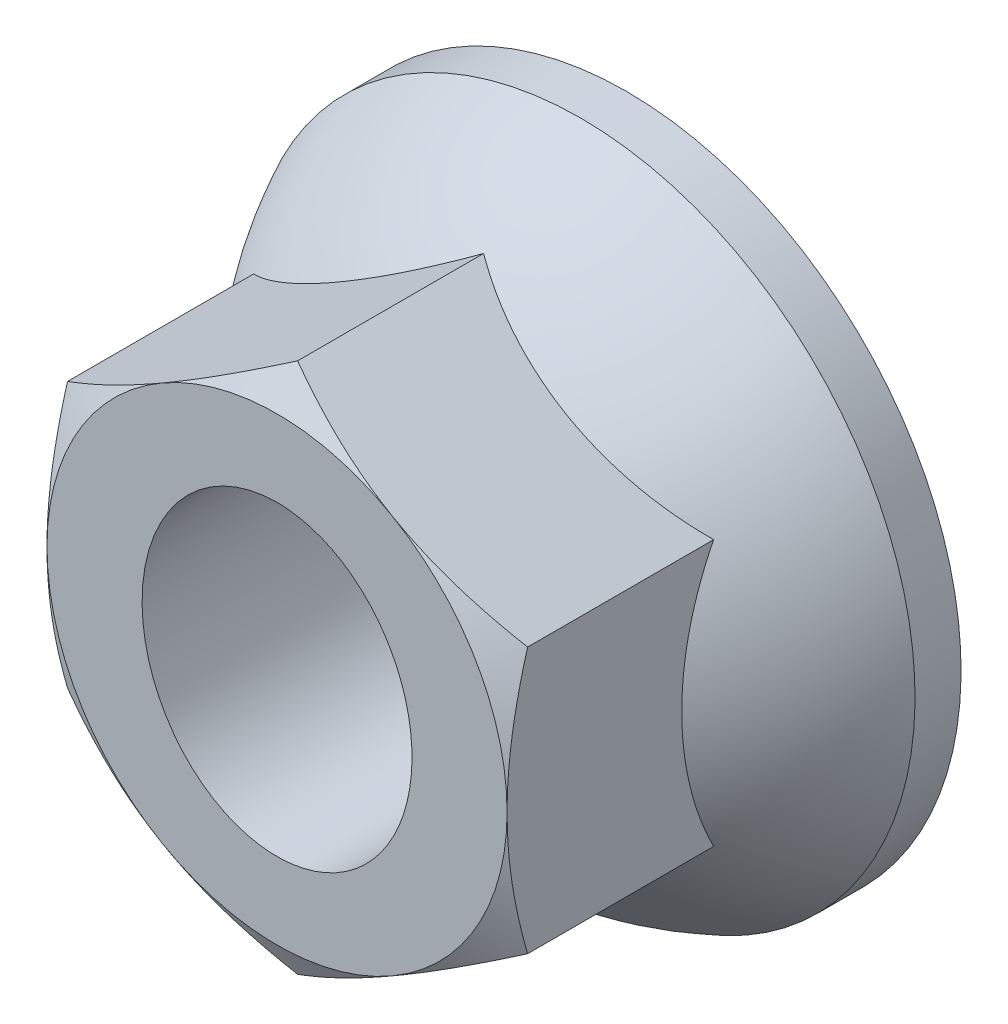
SolidWorks part; units mm, degrees
ref_plane "Front" through (0, 0, 0) normal (0, 0, 1) x (1, 0, 0)
ref_plane "Top" through (0, 0, 0) normal (0, 1, 0) x (1, 0, 0)
ref_plane "Right" through (0, 0, 0) normal (1, 0, 0) x (0, 0, -1)
sketch "Sketch1" plane through (0, 0, 0) normal (1, 0, 0) x (0, 0, -1)
  line L0 (0, 0) -> (5.7, 0) construction
  line L1 (0, 0) -> (-5.7, 0) construction
  line L2 (-5.7, 0) -> (-5.7, 7.5) construction
  line L3 (-5.7, 0) -> (-5.7, -7.5) construction
  line L4 (5.7, 0) -> (5.7, 5) construction
  line L5 (5.7, 0) -> (5.7, -5) construction
  line L6 (5.6062, 5.1624) -> (6.3562, 3.8633) construction
  line L7 (6.3562, 3.8633) -> (7.1062, 5.1624) construction
  line L8 (7.1062, 5.1624) -> (5.6062, 5.1624) construction
  line L9 (6.3562, 5.1624) -> (6.3562, 5) construction
  line L10 (6.3562, 5) -> (6.3562, 4.0257) construction
  line L11 (6.3562, 4.0257) -> (6.3562, 3.8633) construction
  line L12 (6.3562, 5.0812) -> (7.0594, 5.0812) construction
  line L13 (6.3562, 5.0812) -> (5.6531, 5.0812) construction
  line L14 (5.7, 5) -> (7.0125, 5) construction
  line L15 (6.2625, 4.0257) -> (6.45, 4.0257) construction
  line L20 (5.7, -5) -> (5.7, -10.9) construction
  line L21 (5.7, 5) -> (5.7, 10.9) construction
  line L22 (5.7, 10.9) -> (4.2, 10.9) construction
  line L23 (4.2, 10.9) -> (4.2, 0) construction
  line L24 (4.2, 10.9) -> (-2.6, 10.9) construction
  line L25 (-2.6, 10.9) -> (-2.6, 0) construction
  dimension "Height" = 11.4
  dimension "Width" = 15
  dimension "Thread Size" = 10
  dimension "Thread Pitch" = 1.5
  dimension "D2" = 0.1875
  dimension "Flange Diameter" = 21.8
  dimension "Flange Thickness" = 1.5
  dimension "Hex Height" = 3.1
sketch "Sketch20" plane through (0, 0, 0) normal (0, 0, 1) x (1, 0, 0)
  line L1 (7.5, -4.3301) -> (7.5, 4.3301)
  line L2 (7.5, 4.3301) -> (0, 8.6603)
  line L3 (0, 8.6603) -> (-7.5, 4.3301)
  line L4 (-7.5, 4.3301) -> (-7.5, -4.3301)
  line L5 (-7.5, -4.3301) -> (0, -8.6603)
  line L6 (0, -8.6603) -> (7.5, -4.3301)
  circle A0 centre (0, 0) radius 7.5 construction
  circle A1 centre (0, 0) radius 10.9 construction
  point P10 (0, 10.9)
  dimension "Flange OD" = 21.8
  dimension "Hex" = 15
extrude "Extrude1" add sketch "Sketch20" along normal mid plane 11.4
sketch "Sketch18" plane through (0, 0, 0) normal (1, 0, 0) x (0, 0, -1)
  line L0 (5.7, 0) -> (5.7, 10.9)
  line L1 (5.7, 10.9) -> (4.2, 10.9)
  line L2 (-2.6, 0) -> (5.7, 0) construction
  line L3 (-2.6, 0) -> (-2.6, -0.745) construction
  line L4 (5.7, -4.3301) -> (5.7, 4.3301) construction
  line L6 (5.7, 0) -> (-2.6, 0)
  arc A0 (4.2, 10.9) -> (-2.6, 0) centre (9.536, 0) ccw
  dimension "Flange Thickness" = 1.5
revolve "Revolve1" add sketch "Sketch18" angle 360 about L6
sketch "Sketch2" plane through (0, 0, 5.7) normal (0, 0, 1) x (1, 0, 0)
  circle A0 centre (0, 0) radius 7.5 construction
  circle A5 centre (0, 0) radius 7.5
extrude "Cut-Extrude1" cut sketch "Sketch2" against normal through all draft 60 flip side to cut
sketch "Sketch4" plane through (0, 0, -5.7) normal (0, 0, -1) x (-1, 0, 0)
  line L0 (5, 0) -> (4.4, 0) construction
  circle A0 centre (0, 0) radius 5
  circle A1 centre (0, 0) radius 4.4 construction
  dimension "Thread OD" = 10
  dimension "D1" = 0.6
sketch "Sketch5" plane through (0, 0, 5.7) normal (0, 0, -1) x (-1, 0, 0)
  circle A2 centre (0, 0) radius 5 construction
  circle A3 centre (0, 0) radius 5
sketch "Sketch7" [suppressed] plane through (0, 0, -5.7) normal (0, 0, -1) x (-1, 0, 0)
  circle A0 centre (0, 0) radius 5 construction
  circle A1 centre (0, 0) radius 5
extrude "Cut-Extrude10" cut sketch "Sketch5" along normal through all
sketch "Sketch16" plane through (0, 0, 5.7) normal (0, 0, 1) x (1, 0, 0)
  circle A0 centre (0, 0) radius 7.5
  circle A1 centre (0, 0) radius 7.5 construction
  circle A2 centre (0, 0) radius 5 construction
  circle A3 centre (0, 0) radius 4.4 construction
  ellipse E0 centre (0, 0) end of major axis (0, 5) minor radius 4.4
  point P14 (0, -5)
extrude "Extrude2" add sketch "Sketch16" against normal up to surface (11.4 mm away) up to face at (0, 10.9, -5.7)
curve "Helix/Spiral1" [suppressed] pitch 1.5 height 12.9 turns 8.6 parameters "pitch"=1.5
sketch "Sketch9" [suppressed] plane through (0, 0, -7.9375) normal (1, 0, 0) x (0, 0, -1)
  line L0 (-2.2844, 5.0812) -> (-1.675, 4.0257)
  line L1 (-1.675, 4.0257) -> (-1.4875, 4.0257)
  line L2 (-1.4875, 4.0257) -> (-0.8781, 5.0812)
  line L3 (-0.8781, 5.0812) -> (-2.2844, 5.0812)
sweep "Sweep1" [suppressed] add profiles "Sketch9" path "Helix/Spiral1"
sketch "Sketch10" [suppressed] plane through (0, 0, -5.7) normal (0, 0, -1) x (-1, 0, 0)
  line L6 (-7.5, 4.3301) -> (-7.5, -4.3301)
  line L7 (0, 8.6603) -> (-7.5, 4.3301)
  line L8 (7.5, 4.3301) -> (0, 8.6603)
  line L9 (7.5, -4.3301) -> (7.5, 4.3301)
  line L10 (0, -8.6603) -> (7.5, -4.3301)
  line L11 (-7.5, -4.3301) -> (0, -8.6603)
  line L12 (-7.5, 4.3301) -> (-7.5, -4.3301)
  line L13 (0, 8.6603) -> (-7.5, 4.3301)
  line L14 (7.5, 4.3301) -> (0, 8.6603)
  line L15 (7.5, -4.3301) -> (7.5, 4.3301)
  line L16 (0, -8.6603) -> (7.5, -4.3301)
  line L17 (-7.5, -4.3301) -> (0, -8.6603)
  dimension "D1" = 0
extrude "Cut-Extrude4" [suppressed] cut sketch "Sketch10" along normal through all
sketch "Sketch11" [suppressed] plane through (0, 0, 5.7) normal (0, 0, 1) x (1, 0, 0)
  line L6 (7.5, -4.3301) -> (7.5, 4.3301)
  line L7 (7.5, 4.3301) -> (0, 8.6603)
  line L8 (0, 8.6603) -> (-7.5, 4.3301)
  line L9 (-7.5, 4.3301) -> (-7.5, -4.3301)
  line L10 (-7.5, -4.3301) -> (0, -8.6603)
  line L11 (0, -8.6603) -> (7.5, -4.3301)
  line L12 (7.5, -4.3301) -> (7.5, 4.3301)
  line L13 (7.5, 4.3301) -> (0, 8.6603)
  line L14 (0, 8.6603) -> (-7.5, 4.3301)
  line L15 (-7.5, 4.3301) -> (-7.5, -4.3301)
  line L16 (-7.5, -4.3301) -> (0, -8.6603)
  line L17 (0, -8.6603) -> (7.5, -4.3301)
  dimension "D1" = 0
extrude "Cut-Extrude5" [suppressed] cut sketch "Sketch11" along normal through all
sketch "Sketch13" [suppressed] plane through (0, 0, 5.7) normal (0, 0, 1) x (1, 0, 0)
  spline S0 degree 3 poles (-0.3161, -5.0762) (0.3161, -5.0762) (0.6258, -5.0387) (1.2327, -4.8926) (1.5319, -4.7823) (2.0899, -4.5024) (2.3537, -4.3314) (2.8434, -3.9355) (3.0645, -3.715) (3.4632, -3.2332) (3.6412, -2.9702) (3.9434, -2.4238) (4.0695, -2.1384) (4.2734, -1.5439) (4.3497, -1.2387) (4.4508, -0.6242) (4.4763, -0.3132) (4.476, 0.6313) (4.3757, 1.246) (4.0694, 2.1385) (3.9425, 2.4252) (3.6424, 2.9682) (3.4686, 3.2259) (3.0686, 3.7108) (2.8456, 3.933) (2.3639, 4.3238) (2.1037, 4.4945) (1.5393, 4.7795) (1.2466, 4.888) (0.7934, 4.9989) (0.6398, 5.0273) (0.3275, 5.0657) (0.169, 5.0757) (-0.3005, 5.0772) (-0.6105, 5.0413) (-1.224, 4.8957) (-1.52, 4.7872) (-2.0798, 4.5085) (-2.3476, 4.3355) (-2.8352, 3.9429) (-3.0575, 3.7227) (-3.461, 3.2367) (-3.6367, 2.9774) (-3.9399, 2.431) (-4.0684, 2.1408) (-4.2723, 1.548) (-4.3482, 1.2454) (-4.4504, 0.6285) (-4.4762, 0.3119) (-4.4762, -0.3131) (-4.4509, -0.6234) (-4.3495, -1.2397) (-4.2722, -1.5481) (-4.0692, -2.1387) (-3.9437, -2.4229) (-3.6423, -2.9684) (-3.4639, -3.2323) (-3.0656, -3.7138) (-2.8458, -3.933) (-2.3616, -4.3255) (-2.0937, -4.5002) (-1.5359, -4.7806) (-1.2443, -4.889) (-0.6335, -5.0376) (-0.3161, -5.0762) (0.3161, -5.0762) (0.6258, -5.0387) knots -0.03125 -0.03125 0 0 0.03125 0.03125 0.0625 0.0625 0.09375 0.09375 0.125 0.125 0.15625 0.15625 0.1875 0.1875 0.21875 0.21875 0.25 0.25 0.3125 0.3125 0.34375 0.34375 0.375 0.375 0.40625 0.40625 0.4375 0.4375 0.46875 0.46875 0.484375 0.484375 0.5 0.5 0.53125 0.53125 0.5625 0.5625 0.59375 0.59375 0.625 0.625 0.65625 0.65625 0.6875 0.6875 0.71875 0.71875 0.75 0.75 0.78125 0.78125 0.8125 0.8125 0.84375 0.84375 0.875 0.875 0.90625 0.90625 0.9375 0.9375 0.96875 0.96875 1 1 1.03125 1.03125 1.0625 only from (0, -5.0762) to (0, -5.0762)
  spline S1 degree 3 poles (-0.3161, -5.0762) (0.3161, -5.0762) (0.6258, -5.0387) (1.2327, -4.8926) (1.5319, -4.7823) (2.0899, -4.5024) (2.3537, -4.3314) (2.8434, -3.9355) (3.0645, -3.715) (3.4632, -3.2332) (3.6412, -2.9702) (3.9434, -2.4238) (4.0695, -2.1384) (4.2734, -1.5439) (4.3497, -1.2387) (4.4508, -0.6242) (4.4763, -0.3132) (4.476, 0.6313) (4.3757, 1.246) (4.0694, 2.1385) (3.9425, 2.4252) (3.6424, 2.9682) (3.4686, 3.2259) (3.0686, 3.7108) (2.8456, 3.933) (2.3639, 4.3238) (2.1037, 4.4945) (1.5393, 4.7795) (1.2466, 4.888) (0.7934, 4.9989) (0.6398, 5.0273) (0.3275, 5.0657) (0.169, 5.0757) (-0.3005, 5.0772) (-0.6105, 5.0413) (-1.224, 4.8957) (-1.52, 4.7872) (-2.0798, 4.5085) (-2.3476, 4.3355) (-2.8352, 3.9429) (-3.0575, 3.7227) (-3.461, 3.2367) (-3.6367, 2.9774) (-3.9399, 2.431) (-4.0684, 2.1408) (-4.2723, 1.548) (-4.3482, 1.2454) (-4.4504, 0.6285) (-4.4762, 0.3119) (-4.4762, -0.3131) (-4.4509, -0.6234) (-4.3495, -1.2397) (-4.2722, -1.5481) (-4.0692, -2.1387) (-3.9437, -2.4229) (-3.6423, -2.9684) (-3.4639, -3.2323) (-3.0656, -3.7138) (-2.8458, -3.933) (-2.3616, -4.3255) (-2.0937, -4.5002) (-1.5359, -4.7806) (-1.2443, -4.889) (-0.6335, -5.0376) (-0.3161, -5.0762) (0.3161, -5.0762) (0.6258, -5.0387) knots -0.03125 -0.03125 0 0 0.03125 0.03125 0.0625 0.0625 0.09375 0.09375 0.125 0.125 0.15625 0.15625 0.1875 0.1875 0.21875 0.21875 0.25 0.25 0.3125 0.3125 0.34375 0.34375 0.375 0.375 0.40625 0.40625 0.4375 0.4375 0.46875 0.46875 0.484375 0.484375 0.5 0.5 0.53125 0.53125 0.5625 0.5625 0.59375 0.59375 0.625 0.625 0.65625 0.65625 0.6875 0.6875 0.71875 0.71875 0.75 0.75 0.78125 0.78125 0.8125 0.8125 0.84375 0.84375 0.875 0.875 0.90625 0.90625 0.9375 0.9375 0.96875 0.96875 1 1 1.03125 1.03125 1.0625 only from (0, -5.0762) to (0, -5.0762)
  dimension "D1" = 0.0762
extrude "Cut-Extrude8" [suppressed] cut sketch "Sketch13" against normal blind 2.625 draft 45
sketch "Sketch14" [suppressed] plane through (0, 0, -5.7) normal (0, 0, -1) x (-1, 0, 0)
  spline S1 degree 3 poles (-0.3161, -5.0762) (0.3161, -5.0762) (0.6335, -5.0376) (1.2443, -4.889) (1.5359, -4.7806) (2.0937, -4.5002) (2.3616, -4.3255) (2.8458, -3.933) (3.0656, -3.7138) (3.4639, -3.2323) (3.6423, -2.9684) (3.9437, -2.4229) (4.0692, -2.1387) (4.2722, -1.5481) (4.3495, -1.2397) (4.4509, -0.6234) (4.4762, -0.3131) (4.4762, 0.3119) (4.4504, 0.6285) (4.3482, 1.2454) (4.2723, 1.548) (4.0684, 2.1408) (3.9399, 2.431) (3.6367, 2.9774) (3.461, 3.2367) (3.0575, 3.7227) (2.8352, 3.9429) (2.3476, 4.3355) (2.0798, 4.5085) (1.52, 4.7872) (1.224, 4.8957) (0.6105, 5.0413) (0.3005, 5.0772) (-0.169, 5.0757) (-0.3275, 5.0657) (-0.6398, 5.0273) (-0.7934, 4.9989) (-1.2466, 4.888) (-1.5393, 4.7795) (-2.1037, 4.4945) (-2.3639, 4.3238) (-2.8456, 3.933) (-3.0686, 3.7108) (-3.4686, 3.2259) (-3.6424, 2.9682) (-3.9425, 2.4252) (-4.0694, 2.1385) (-4.3757, 1.246) (-4.476, 0.6313) (-4.4763, -0.3132) (-4.4508, -0.6242) (-4.3497, -1.2387) (-4.2734, -1.5439) (-4.0695, -2.1384) (-3.9434, -2.4238) (-3.6412, -2.9702) (-3.4632, -3.2332) (-3.0645, -3.715) (-2.8434, -3.9355) (-2.3537, -4.3314) (-2.0899, -4.5024) (-1.5319, -4.7823) (-1.2327, -4.8926) (-0.6258, -5.0387) (-0.3161, -5.0762) (0.3161, -5.0762) (0.6335, -5.0376) knots -0.03125 -0.03125 0 0 0.03125 0.03125 0.0625 0.0625 0.09375 0.09375 0.125 0.125 0.15625 0.15625 0.1875 0.1875 0.21875 0.21875 0.25 0.25 0.28125 0.28125 0.3125 0.3125 0.34375 0.34375 0.375 0.375 0.40625 0.40625 0.4375 0.4375 0.46875 0.46875 0.5 0.5 0.515625 0.515625 0.53125 0.53125 0.5625 0.5625 0.59375 0.59375 0.625 0.625 0.65625 0.65625 0.6875 0.6875 0.75 0.75 0.78125 0.78125 0.8125 0.8125 0.84375 0.84375 0.875 0.875 0.90625 0.90625 0.9375 0.9375 0.96875 0.96875 1 1 1.03125 1.03125 1.0625 only from (0, -5.0762) to (0, -5.0762)
  spline S2 degree 3 poles (-0.3161, -5.0762) (0.3161, -5.0762) (0.6335, -5.0376) (1.2443, -4.889) (1.5359, -4.7806) (2.0937, -4.5002) (2.3616, -4.3255) (2.8458, -3.933) (3.0656, -3.7138) (3.4639, -3.2323) (3.6423, -2.9684) (3.9437, -2.4229) (4.0692, -2.1387) (4.2722, -1.5481) (4.3495, -1.2397) (4.4509, -0.6234) (4.4762, -0.3131) (4.4762, 0.3119) (4.4504, 0.6285) (4.3482, 1.2454) (4.2723, 1.548) (4.0684, 2.1408) (3.9399, 2.431) (3.6367, 2.9774) (3.461, 3.2367) (3.0575, 3.7227) (2.8352, 3.9429) (2.3476, 4.3355) (2.0798, 4.5085) (1.52, 4.7872) (1.224, 4.8957) (0.6105, 5.0413) (0.3005, 5.0772) (-0.169, 5.0757) (-0.3275, 5.0657) (-0.6398, 5.0273) (-0.7934, 4.9989) (-1.2466, 4.888) (-1.5393, 4.7795) (-2.1037, 4.4945) (-2.3639, 4.3238) (-2.8456, 3.933) (-3.0686, 3.7108) (-3.4686, 3.2259) (-3.6424, 2.9682) (-3.9425, 2.4252) (-4.0694, 2.1385) (-4.3757, 1.246) (-4.476, 0.6313) (-4.4763, -0.3132) (-4.4508, -0.6242) (-4.3497, -1.2387) (-4.2734, -1.5439) (-4.0695, -2.1384) (-3.9434, -2.4238) (-3.6412, -2.9702) (-3.4632, -3.2332) (-3.0645, -3.715) (-2.8434, -3.9355) (-2.3537, -4.3314) (-2.0899, -4.5024) (-1.5319, -4.7823) (-1.2327, -4.8926) (-0.6258, -5.0387) (-0.3161, -5.0762) (0.3161, -5.0762) (0.6335, -5.0376) knots -0.03125 -0.03125 0 0 0.03125 0.03125 0.0625 0.0625 0.09375 0.09375 0.125 0.125 0.15625 0.15625 0.1875 0.1875 0.21875 0.21875 0.25 0.25 0.28125 0.28125 0.3125 0.3125 0.34375 0.34375 0.375 0.375 0.40625 0.40625 0.4375 0.4375 0.46875 0.46875 0.5 0.5 0.515625 0.515625 0.53125 0.53125 0.5625 0.5625 0.59375 0.59375 0.625 0.625 0.65625 0.65625 0.6875 0.6875 0.75 0.75 0.78125 0.78125 0.8125 0.8125 0.84375 0.84375 0.875 0.875 0.90625 0.90625 0.9375 0.9375 0.96875 0.96875 1 1 1.03125 1.03125 1.0625 only from (0, -5.0762) to (0, -5.0762)
  dimension "D1" = 0
extrude "Cut-Extrude9" [suppressed] cut sketch "Sketch14" against normal blind 2.625 draft 45
equation "\"D3@Helix/Spiral1\"=\"height@Extrude1\"+\"pitch@Helix/Spiral1\""
equation "\"D1@Cut-Extrude8\" = \"pitch@Helix/Spiral1\"*1.750"
equation "\"D1@Cut-Extrude9\" = \"D1@Cut-Extrude8\""
equation "\"D1@Sketch4\"=\"Thread Pitch@Sketch1\"*.4"
equation "\"D2@Sketch1\" = \"Thread Pitch@Sketch1\" / 8"
equation "\"height@Extrude1\"=\"Height@Sketch1\""
equation "\"Hex@Sketch20\"=\"Width@Sketch1\""
equation "\"Flange OD@Sketch20\"=\"Flange Diameter@Sketch1\""
equation "\"Flange Thickness@Sketch18\"=\"Flange Thickness@Sketch1\""
equation "\"Thread OD@Sketch4\"=\"Thread Size@Sketch1\""
equation "\"pitch@Helix/Spiral1\"=\"Thread Pitch@Sketch1\""
